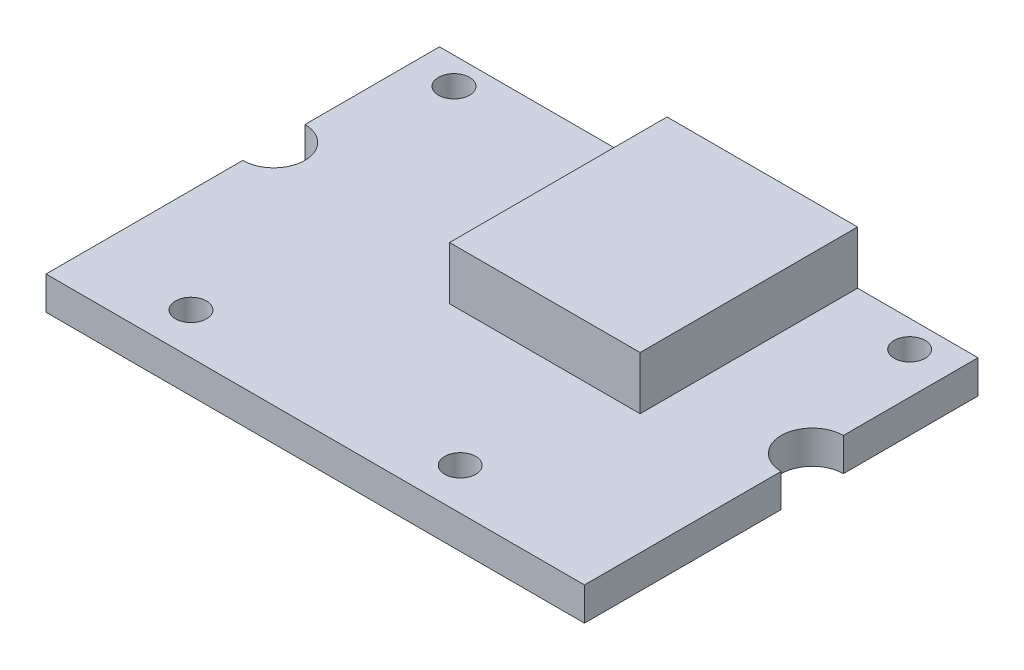
SolidWorks part; units mm, degrees
ref_plane "Front Plane" through (0, 0, 0) normal (0, 0, 1) x (1, 0, 0)
ref_plane "Top Plane" through (0, 0, 0) normal (0, 1, 0) x (1, 0, 0)
ref_plane "Right Plane" through (0, 0, 0) normal (1, 0, 0) x (0, 0, -1)
ref_axis "X-Axis" through (-88.99, 0, 0) along (1, 0, 0)
ref_axis "Y-Axis" through (0, 55, 0) along (0, -1, 0)
ref_axis "Z-Axis" through (0, 0, -88.99) along (0, 0, 1)
sketch "Sketch1" plane through (0, 0, 0) normal (0, 1, 0) x (1, 0, 0)
  line L1 (-13, -9.5) -> (13, -9.5)
  line L2 (-13, -9.5) -> (-13, 9.5)
  line L3 (-13, 9.5) -> (13, 9.5)
  line L4 (13, -9.5) -> (13, 9.5)
  line L5 (-13, -9.5) -> (13, 9.5) construction
  line L6 (-13, 9.5) -> (13, -9.5) construction
  point P0 (0, 0)
  dimension "D1" = 26
  dimension "D2" = 19
extrude "Boss-Extrude1" add sketch "Sketch1" along normal blind 1.6
sketch "Sketch2" plane through (0, 1.6, 0) normal (0, 1, 0) x (1, 0, 0)
  line L0 (13, 9.5) -> (-13, 9.5) construction
  line L1 (-2.0151, 9.5) -> (7.1849, 9.5)
  line L2 (-2.0151, 9.5) -> (-2.0151, -1)
  line L3 (-2.0151, -1) -> (7.1849, -1)
  line L4 (7.1849, 9.5) -> (7.1849, -1)
  dimension "D1" = 9.2
  dimension "D2" = 10.5
extrude "Boss-Extrude2" add sketch "Sketch2" along normal blind 2.56
sketch "Sketch3" plane through (0, 1.6, 0) normal (0, 1, 0) x (1, 0, 0)
  line L0 (-13, -7.5) -> (-8, -7.5) construction
  line L4 (-13, 9.5) -> (-13, -9.5) construction
  line L5 (-8, -7.5) -> (5, -7.5) construction
  line L6 (5, -7.5) -> (13, -7.5) construction
  line L7 (13, -9.5) -> (13, 9.5) construction
  line L8 (-13, -9.5) -> (13, -9.5) construction
  circle A0 centre (-8, -7.5) radius 0.75
  circle A1 centre (5, -7.5) radius 0.75
  dimension "D2" = 1.5
  dimension "D1" = 5
  dimension "D3" = 2
  dimension "D4" = 8
extrude "Cut-Extrude1" cut sketch "Sketch3" against normal through all
sketch "Sketch4" plane through (0, 1.6, 0) normal (0, 1, 0) x (1, 0, 0)
  line L0 (-13, 1.5) -> (13, 1.5) construction
  line L1 (-13, 9.5) -> (-13, -9.5) construction
  line L2 (13, -9.5) -> (13, 9.5) construction
  line L3 (13, 9.5) -> (7.1849, 9.5) construction
  circle A0 centre (-13, 1.5) radius 1.5
  circle A1 centre (13, 1.5) radius 1.5
  dimension "D1" = 3
  dimension "D2" = 8
extrude "Cut-Extrude2" cut sketch "Sketch4" against normal through all
sketch "Sketch5" plane through (0, 1.6, 0) normal (0, 1, 0) x (1, 0, 0)
  line L0 (-13, 8.2) -> (13, 8.2) construction
  line L1 (-13, 9.5) -> (-13, 3) construction
  line L2 (13, 3) -> (13, 9.5) construction
  line L3 (13, 9.5) -> (7.1849, 9.5) construction
  circle A0 centre (-11, 8.2) radius 0.75
  circle A1 centre (11, 8.2) radius 0.75
  dimension "D2" = 1.5
  dimension "D1" = 1.3
  dimension "D3" = 2
  dimension "D4" = 2
extrude "Cut-Extrude3" cut sketch "Sketch5" against normal through all
equation "\"D4@Sketch5\"=\"D3@Sketch5\""
